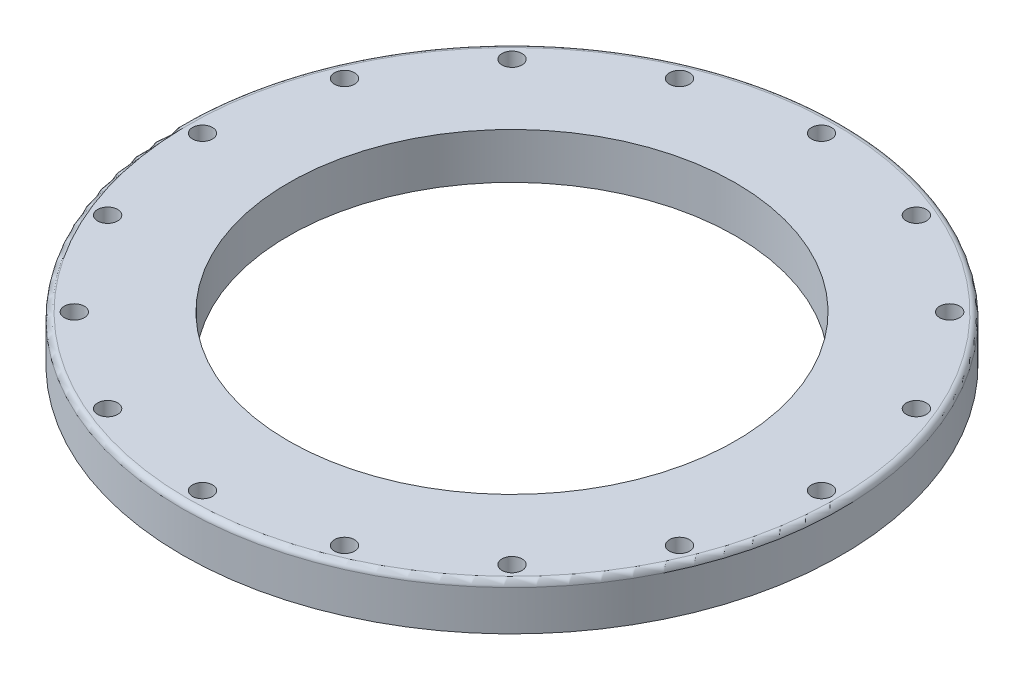
SolidWorks part; units mm, degrees
ref_plane "Front Plane" through (0, 0, 0) normal (0, 0, 1) x (1, 0, 0)
ref_plane "Top Plane" through (0, 0, 0) normal (0, 1, 0) x (1, 0, 0)
ref_plane "Right Plane" through (0, 0, 0) normal (1, 0, 0) x (0, 0, -1)
sketch "Sketch1" plane through (0, 0, 0) normal (0, 1, 0) x (1, 0, 0)
  circle A0 centre (0, 0) radius 57.5
  circle A1 centre (0, 0) radius 39
  dimension "D1" = 78
  dimension "D2" = 115
extrude "Boss-Extrude1" add sketch "Sketch1" along normal blind 8
sketch "Sketch2" plane through (0, 8, 0) normal (0, 1, 0) x (1, 0, 0)
  circle A0 centre (0, 0) radius 54 construction
  circle A1 centre (0, 54) radius 1.75
  circle A2 centre (20.6649, 49.8895) radius 1.75
  circle A3 centre (38.1838, 38.1838) radius 1.75
  circle A4 centre (49.8895, 20.6649) radius 1.75
  circle A5 centre (54, 0) radius 1.75
  circle A6 centre (49.8895, -20.6649) radius 1.75
  circle A7 centre (38.1838, -38.1838) radius 1.75
  circle A8 centre (20.6649, -49.8895) radius 1.75
  circle A9 centre (0, -54) radius 1.75
  circle A10 centre (-20.6649, -49.8895) radius 1.75
  circle A11 centre (-38.1838, -38.1838) radius 1.75
  circle A12 centre (-49.8895, -20.6649) radius 1.75
  circle A13 centre (-54, 0) radius 1.75
  circle A14 centre (-49.8895, 20.6649) radius 1.75
  circle A15 centre (-38.1838, 38.1838) radius 1.75
  circle A16 centre (-20.6649, 49.8895) radius 1.75
  point P37 (0, 0)
  dimension "D1" = 108
  dimension "D2" = 3.5
  dimension "D3" = 16
extrude "Cut-Extrude1" cut sketch "Sketch2" against normal blind 25
fillet "Fillet1" radius 1 1 edges at (0, 8, 57.5)
